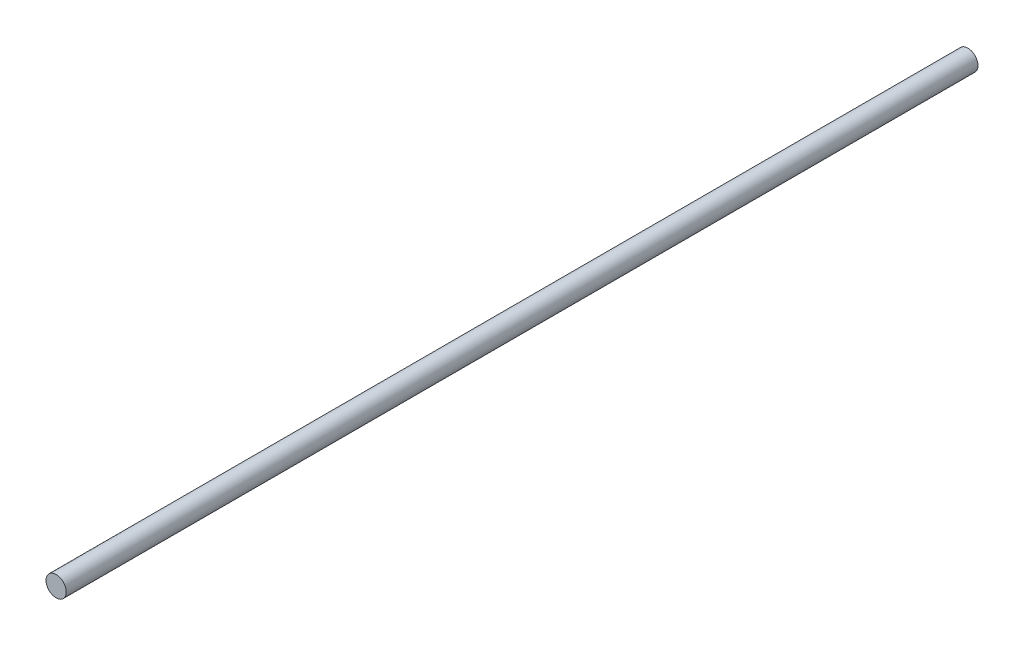
SolidWorks part; units mm, degrees
ref_plane "Front Plane" through (0, 0, 0) normal (0, 0, 1) x (1, 0, 0)
ref_plane "Top Plane" through (0, 0, 0) normal (0, 1, 0) x (1, 0, 0)
ref_plane "Right Plane" through (0, 0, 0) normal (1, 0, 0) x (0, 0, -1)
sketch "Sketch1" plane through (0, 0, 0) normal (0, 0, 1) x (1, 0, 0)
  circle A1 centre (20, 0) radius 1
extrude "Boss-Extrude1" add sketch "Sketch1" against normal blind 90
